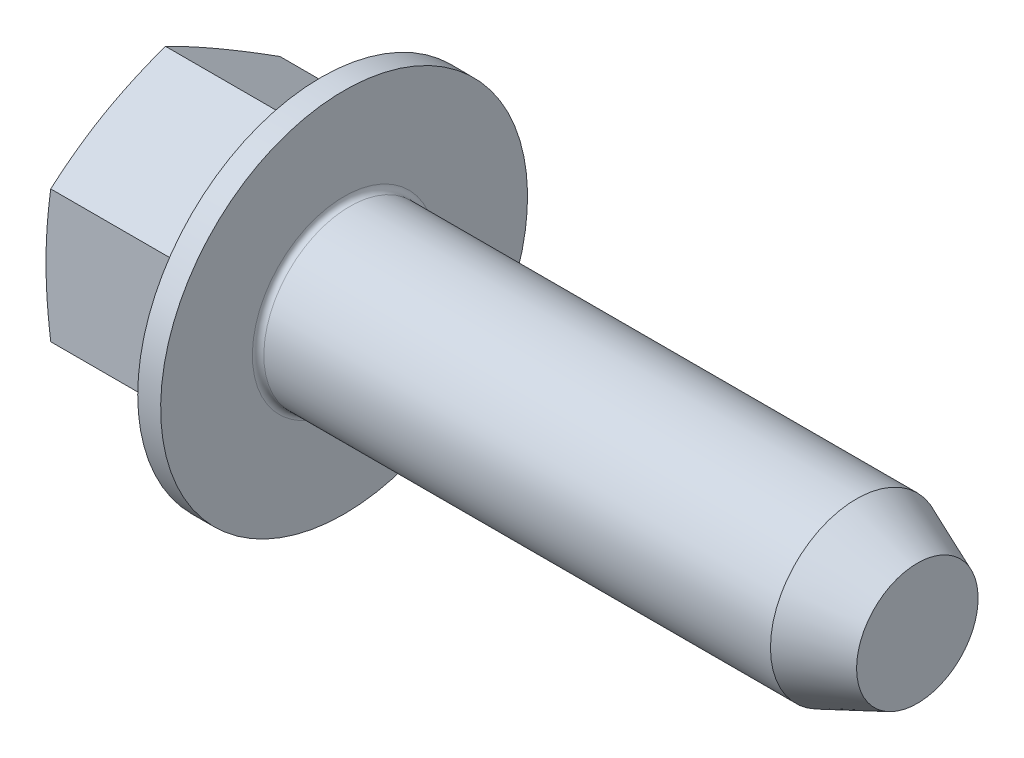
SolidWorks part; units mm, degrees
ref_plane "Front Plane" through (0, 0, 0) normal (0, 0, 1) x (1, 0, 0)
ref_plane "Top Plane" through (0, 0, 0) normal (0, 1, 0) x (1, 0, 0)
ref_plane "Right Plane" through (0, 0, 0) normal (1, 0, 0) x (0, 0, -1)
sketch "Sketch1" plane through (0, 0, 0) normal (0, 0, 1) x (1, 0, 0)
  line L0 (0, 0) -> (10, 0) construction
  line L1 (0, 0) -> (-3.2, 0) construction
  line L2 (0.1, 1.5) -> (9.7195, 1.5)
  line L3 (10, 0) -> (10, 1.2195)
  line L4 (0, 1.6) -> (0, 3.2)
  line L5 (0, 3.2) -> (-0.4, 3.2)
  line L6 (-0.4, 3.2) -> (-0.7215, 2)
  line L7 (-0.7215, 2) -> (-3.2, 2)
  line L8 (-3.2, 2) -> (-3.2, 1.6)
  line L9 (-3.2, 1.6) -> (-2.8, 1.6)
  line L10 (-2.8, 1.6) -> (-2.8, 0)
  line L11 (-2.8, 0) -> (10, 0)
  line L12 (-2.8, 0) -> (-2.8, 1.98) construction
  line L14 (10, 1.2195) -> (9.7195, 1.5)
  line L15 (10, 0) -> (1, 0) construction
  arc A0 (0.1, 1.5) -> (0, 1.6) centre (0.1, 1.6) cw
  dimension "D7" = 0.1
  dimension "L" = 10
  dimension "K" = 3.2
  dimension "s" = 4
  dimension "dia" = 3
  dimension "D1" = 3.2
  dimension "D2" = 0.4
  dimension "c" = 0.4
  dimension "D4" = 15
  dimension "D5" = 45
  dimension "min" = 2.439
  dimension "B" = 9
  dimension "Dc" = 6.4
revolve "Revolve1" add sketch "Sketch1" angle 360 about L11
cosmetic thread "Cosmetic Thread1" [suppressed] parameters "D1"=8.6195, "D2"=2.439
sketch "Sketch2" plane through (-3.2, 0, 0) normal (-1, 0, 0) x (0, 0, 1)
  line L1 (0, 2.3094) -> (-2, 1.1547)
  line L2 (-2, 1.1547) -> (-2, -1.1547)
  line L3 (-2, -1.1547) -> (0, -2.3094)
  line L4 (0, -2.3094) -> (2, -1.1547)
  line L5 (2, -1.1547) -> (2, 1.1547)
  line L6 (2, 1.1547) -> (0, 2.3094)
  circle A0 centre (0, 0) radius 1.6 construction
  circle A1 centre (0, 0) radius 1.6
  circle A2 centre (0, 0) radius 2 construction
  circle A3 centre (0, 0) radius 2 construction
extrude "Extrude1" add sketch "Sketch2" against normal up to next (3.2 mm away)
sketch "Sketch3" plane through (0, 0, 0) normal (0, 1, 0) x (1, 0, 0)
  line L0 (-3.4679, 1) -> (-2.9321, 3)
  line L1 (-3.2, 0) -> (-3.2, 2) construction
  line L2 (0, 0) -> (-3.6033, 0) construction
  line L3 (-2.9321, 3) -> (-3.4679, 3)
  line L4 (-3.4679, 3) -> (-3.4679, 1)
  dimension "D1" = 15
  dimension "D2" = 2
revolve "Cut-Revolve1" cut sketch "Sketch3" angle 360 about L2
fillet "Fillet1" radius 0.2 6 edges
sketch "Sketch4" plane through (0, 0, 0) normal (0, 0, 1) x (1, 0, 0)
  line L0 (0, 0) -> (5.3731, 0) construction
  line L1 (10, -1.2195) -> (10, 1.2195) construction
  line L3 (10, 1.06) -> (8.9377, 1.5)
  line L4 (0.1, 1.5) -> (9.7195, 1.5) construction
  line L5 (8.9377, 1.5) -> (8.9377, 2)
  line L6 (8.9377, 2) -> (10, 2)
  line L7 (10, 2) -> (10, 1.06)
  dimension "D1" = 0.5
  dimension "D2" = 22.5
  dimension "Dp" = 2.12
revolve "Cut-Revolve2" cut sketch "Sketch4" angle 360 about L0
sketch "Sketch5" plane through (0, 0, 0) normal (0, 0, 1) x (1, 0, 0)
  line L0 (10, 0) -> (1.3805, 0) construction
  line L1 (-2.8, 0) -> (10, 0) construction
  line L2 (1.5424, 1.2195) -> (1.7044, 1.5)
  line L3 (1.7044, 1.5) -> (1.7044, 1.8239)
  line L4 (1.7044, 1.8239) -> (1.3805, 1.8239)
  line L5 (1.3805, 1.8239) -> (1.3805, 1.5)
  line L6 (1.3805, 1.5) -> (1.5424, 1.2195)
  dimension "B" = 8.6195
  dimension "D1" = 2.439
  dimension "D2" = 3
revolve "Cut-Revolve10" [suppressed] cut sketch "Sketch5" angle 360 about L0
pattern_linear "LPattern10" [suppressed] count 18 spacing 0.5 along (1, 0, 0) of bodies 111
equation "\"D1@Sketch1\" = \"s@Sketch1\" / 10 * 8"
equation "\"D2@Sketch1\" = \"K@Sketch1\" / 8"
equation "\"D2@Sketch3\" = \"s@Sketch1\" / 2"
equation "\"D2@Cosmetic Thread1\" = \"min@Sketch1\""
equation "\"D1@Cosmetic Thread1\" = \"B@Sketch1\" -  ( \"dia@Sketch1\" - \"min@Sketch1\" )  / 2 - \"D7@Sketch1\""
equation "\"D1@Sketch5\" = \"D2@Cosmetic Thread1\""
equation "\"D2@Sketch5\" = \"dia@Sketch1\""
equation "\"B@Sketch5\" = \"D1@Cosmetic Thread1\""
equation "\"D1@LPattern10\" = int( \"D1@Cosmetic Thread1\" / \"D3@LPattern10\" + 0.999 ) "
